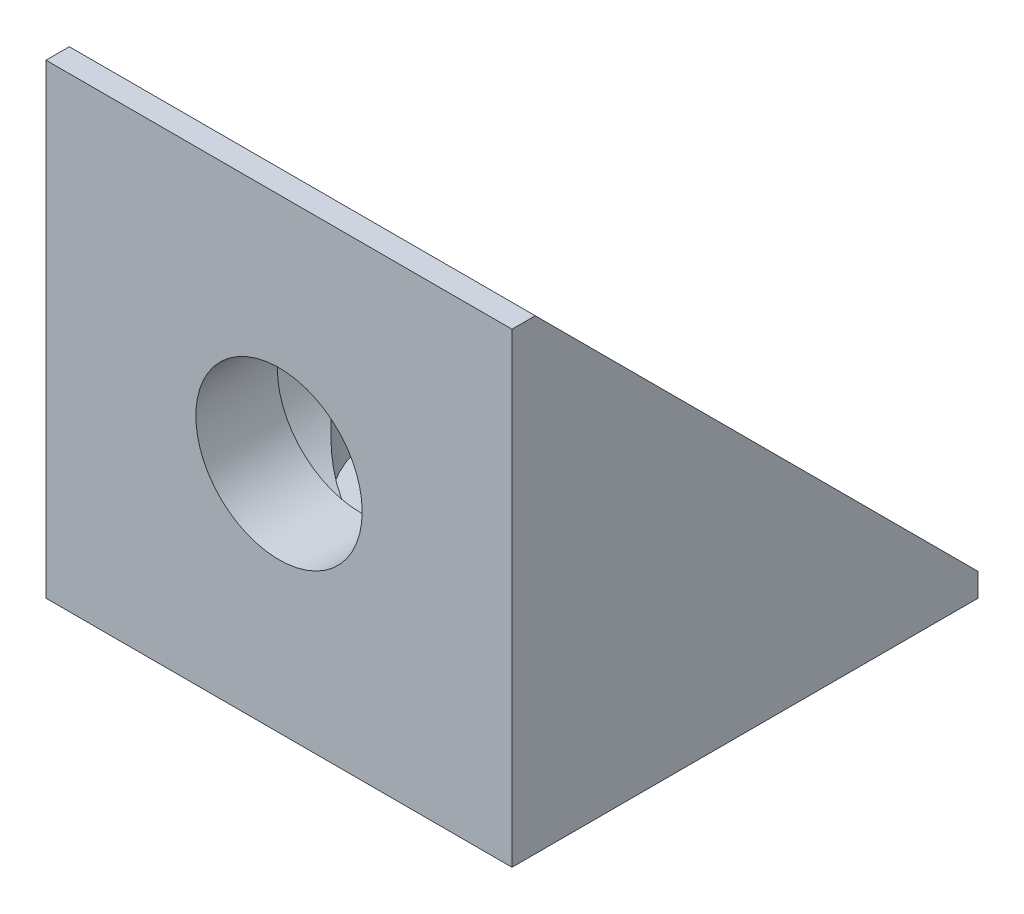
SolidWorks part; units mm, degrees
material "CA"
ref_plane "Plan de face" through (0, 0, 0) normal (0, 0, 1) x (1, 0, 0)
ref_plane "Plan de dessus" through (0, 0, 0) normal (0, 1, 0) x (1, 0, 0)
ref_plane "Plan de droite" through (0, 0, 0) normal (1, 0, 0) x (0, 0, -1)
sketch "Esquisse1" plane through (0, 0, 0) normal (1, 0, 0) x (0, 0, -1)
  line L0 (20, 0) -> (0, 0)
  line L1 (0, 0) -> (0, 20)
  line L2 (0, 20) -> (1, 20)
  line L3 (1, 20) -> (20, 1)
  line L4 (20, 1) -> (20, 0)
  line L5 (10.5, 10.5) -> (0, 0) construction
  line L6 (0, 20) -> (20, 0) construction
  dimension "D1" = 45
  dimension "D2" = 20
  dimension "D3" = 1
extrude "Boss.-Extru.1" add sketch "Esquisse1" along normal mid plane 20
sketch "Esquisse2" plane through (0, 0, 0) normal (0, -1, 0) x (1, 0, 0)
  line L0 (-10, 0) -> (10, -20) construction
  circle A0 centre (0, -10) radius 3.57
  dimension "D1" = 7.14
extrude "Enlèv. mat.-Extru.1" cut sketch "Esquisse2" against normal through all
sketch "Esquisse3" plane through (0, 20, 0) normal (0, 1, 0) x (1, 0, 0)
  circle A0 centre (0, 10) radius 5.5
  dimension "D1" = 11
extrude "Enlèv. mat.-Extru.2" cut sketch "Esquisse3" against normal offset from surface (16.5 mm away) 3.5 up to face at (0, 0, -13.57)
sketch "Esquisse5" plane through (0, 0, 0) normal (0, 0, 1) x (1, 0, 0)
  line L0 (-10, 20) -> (10, 0) construction
  circle A0 centre (0, 10) radius 3.57
  dimension "D1" = 7.14
extrude "Enlèv. mat.-Extru.3" cut sketch "Esquisse5" against normal through all
sketch "Esquisse6" plane through (0, 0, -20) normal (0, 0, -1) x (-1, 0, 0)
  circle A0 centre (0, 10) radius 5.5
  dimension "D1" = 11
extrude "Enlèv. mat.-Extru.4" cut sketch "Esquisse6" against normal offset from surface (16.5 mm away) 3.5 up to face at (3.57, 10, 0)
